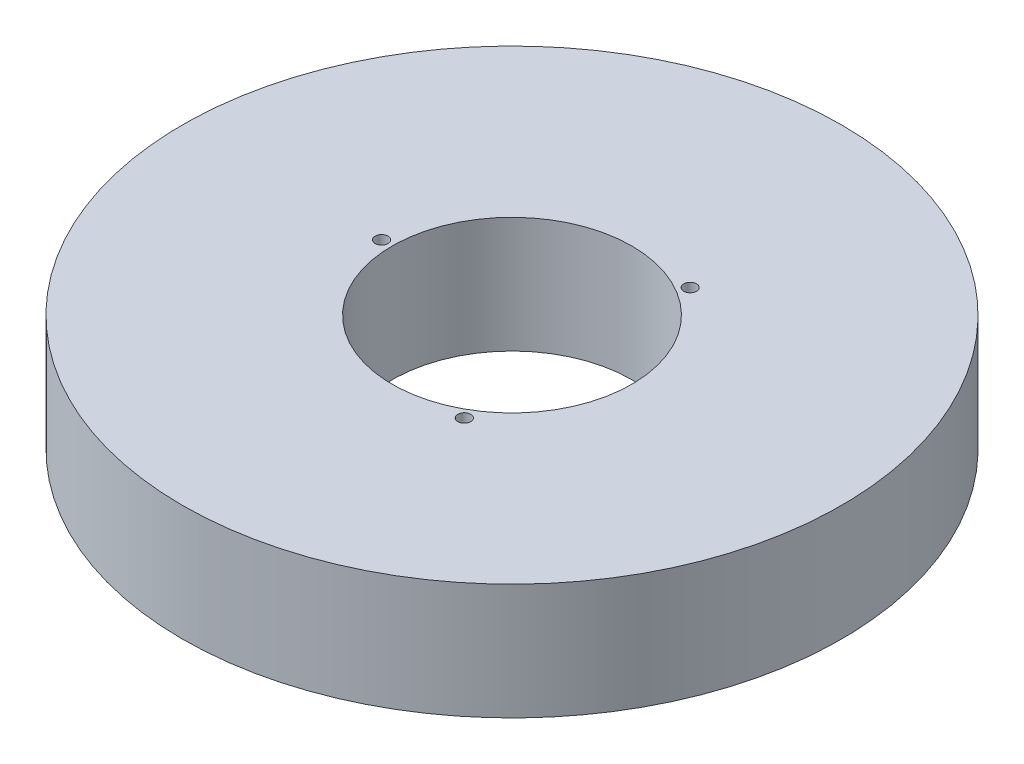
SolidWorks part; units mm, degrees
ref_plane "Front Plane" through (0, 0, 0) normal (0, 0, 1) x (1, 0, 0)
ref_plane "Top Plane" through (0, 0, 0) normal (0, 1, 0) x (1, 0, 0)
ref_plane "Right Plane" through (0, 0, 0) normal (1, 0, 0) x (0, 0, -1)
sketch "Sketch1" plane through (0, 0, 0) normal (0, 1, 0) x (1, 0, 0)
  circle A0 centre (0, 0) radius 82.5
  dimension "FLANGE_OD" = 165
extrude "Boss-Extrude1" add sketch "Sketch1" along normal blind 29
sketch "Sketch2" plane through (0, 0, 0) normal (0, 1, 0) x (1, 0, 0)
  circle A0 centre (0, 0) radius 30
  dimension "BORE_D" = 60
extrude "Cut-Extrude1" cut sketch "Sketch2" along normal through all
sketch "Sketch3" plane through (0, 29, 0) normal (0, 1, 0) x (1, 0, 0)
  circle A0 centre (0, 0) radius 32.6463 construction
  circle A1 centre (-32.6463, 0) radius 1.6137
  dimension "BOLT_D" = 3.2273
  dimension "BOLT_PCD" = 65.2926
extrude "Cut-Extrude2" cut sketch "Sketch3" against normal blind 18.8259
pattern_circular "CirPattern1" count 3 over 360 about axis through (0, 0, 0) along (0, 1, 0) of "Cut-Extrude2"
